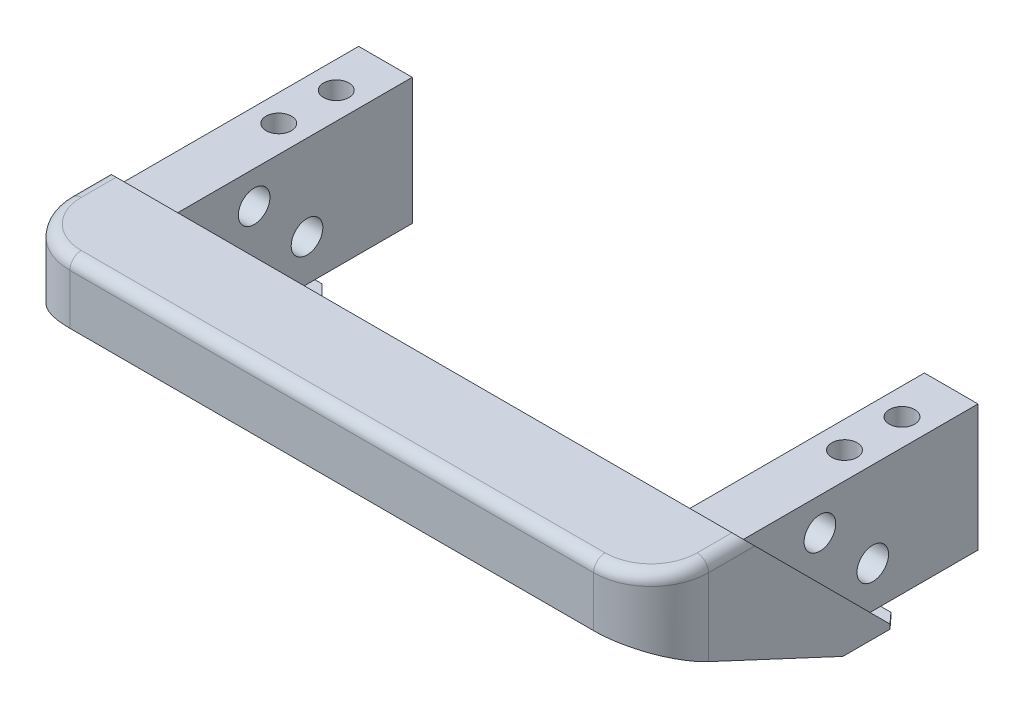
SolidWorks part; units mm, degrees
ref_plane "Front Plane" through (0, 0, 0) normal (0, 0, 1) x (1, 0, 0)
ref_plane "Top Plane" through (0, 0, 0) normal (0, 1, 0) x (1, 0, 0)
ref_plane "Right Plane" through (0, 0, 0) normal (1, 0, 0) x (0, 0, -1)
sketch "Sketch1" plane through (0, 0, 0) normal (1, 0, 0) x (0, 0, -1)
  line L0 (0, 0) -> (0, 50.8)
  line L5 (0, 50.8) -> (50.8, 0)
  line L6 (50.8, 0) -> (0, 0)
  dimension "D1" = 45
  dimension "D2" = 50.8
extrude "Boss-Extrude1" add sketch "Sketch1" along normal blind 222.25
sketch "Sketch3" plane through (0, 0, 0) normal (0, 0, 1) x (1, 0, 0)
  line L0 (196.85, 50.8) -> (196.85, 0) construction
  line L1 (218.875, 47.425) -> (200.225, 47.425)
  line L2 (218.875, 47.425) -> (218.875, 3.375)
  line L3 (218.875, 3.375) -> (200.225, 3.375)
  line L4 (200.225, 47.425) -> (200.225, 3.375)
  line L5 (222.25, 50.8) -> (222.25, 0) construction
  line L6 (222.25, 50.8) -> (0, 50.8) construction
  line L7 (222.25, 0) -> (0, 0) construction
  dimension "D1" = 3.375
  dimension "D2" = 3.375
  dimension "D3" = 3.375
  dimension "D4" = 18.65
  dimension "D5" = 25.4
extrude "Boss-Extrude3" add sketch "Sketch3" against normal blind 85 contours L1 L4 L3 L2 region at (209.55, 25.4, 0)
sketch "Sketch15" plane through (0, 47.425, 0) normal (0, 1, 0) x (1, 0, 0)
  circle A0 centre (209.55, 67.8714) radius 4.4196
  circle A1 centre (209.55, 47.8714) radius 4.4196
  dimension "D1" = 8.8392
  dimension "D2" = 8.8392
extrude "Cut-Extrude6" cut sketch "Sketch15" against normal blind 15
sketch "Sketch16" plane through (200.225, 0, 0) normal (-1, 0, 0) x (0, 0, 1)
  circle A0 centre (-29.9942, 36.0705) radius 5.5
  circle A1 centre (-48.379, 17.6857) radius 5.5
  dimension "D1" = 11
  dimension "D2" = 11
extrude "Cut-Extrude7" cut sketch "Sketch16" against normal through all
ref_plane "Plane1" through (111.125, 0, 0) normal (-1, 0, 0) x (0, 0, 1)
mirror "Mirror1" about plane through (111.125, 0, 0) normal (-1, 0, 0) of "Cut-Extrude7", "Boss-Extrude3", "Cut-Extrude6"
sketch "Sketch4" plane through (222.25, 0, 0) normal (1, 0, 0) x (0, 0, -1)
  line L0 (-5, 50.8) -> (-26.1464, 36.606)
  line L3 (0, 0) -> (0, 50.8)
  line L4 (0, 50.8) -> (-5, 50.8)
  line L5 (0, 0) -> (-5, 0)
  line L6 (-15, 0) -> (-5, 0)
  line L7 (-5, 50.8) -> (-5, 0) construction
  arc A0 (-15, 0) -> (-26.1464, 36.606) centre (-15, 20) cw
  dimension "D2" = 20
  dimension "D1" = 10
  dimension "D3" = 5
extrude "Boss-Extrude4" [suppressed] add sketch "Sketch4" against normal up to surface (222.25 mm away) up to face at (0, 16.9333, -16.9333)
sketch "Sketch7" plane through (222.25, 0, 0) normal (1, 0, 0) x (0, 0, -1)
  line L0 (0, 50.8) -> (-32.1286, 50.8)
  line L2 (-32.1286, 29.3441) -> (30.8, 0)
  line L3 (0, 0) -> (50.8, 0) construction
  line L4 (30.8, 0) -> (50.8, 0)
  line L5 (50.8, 0) -> (0, 50.8)
  line L8 (-32.1286, 50.8) -> (-32.1286, 29.3441)
  point P1 (-32.1286, 29.3234)
  dimension "D1" = 20
  dimension "D2" = 20
  dimension "D3" = 32.1286
extrude "Boss-Extrude5" add sketch "Sketch7" against normal up to surface (222.25 mm away) up to face at (0, 16.9333, -16.9333)
sketch "Sketch8" plane through (222.25, 0, 0) normal (1, 0, 0) x (0, 0, -1)
  line L0 (-32.1286, 29.3441) -> (30.8, 0) construction
  line L1 (0, 14.3623) -> (30.8, 0)
  line L2 (0, 14.3623) -> (0, 0)
  line L3 (0, 0) -> (30.8, 0)
extrude "Cut-Extrude3" cut sketch "Sketch8" against normal up to surface (222.25 mm away) up to face at (0, 24.2177, 2.2429)
sketch "Sketch9" plane through (222.25, 0, 0) normal (1, 0, 0) x (0, 0, -1)
  line L0 (50.8, 0) -> (73.6991, 0) construction
  line L1 (50.8, 0) -> (51, -0.2)
  line L2 (30.8, 0) -> (34.6333, -1.7875)
  line L3 (-32.1286, 29.3441) -> (30.8, 0) construction
  line L4 (50.8, 0) -> (0, 50.8) construction
  line L5 (51, -0.2) -> (54.7, -0.2)
  line L6 (54.7, -0.2) -> (54.7, -1.7875)
  line L7 (54.7, -1.7875) -> (34.6333, -1.7875)
  line L8 (30.8, 0) -> (50.8, 0) construction
  line L9 (30.8, 0) -> (50.8, 0)
  line M9 (30.8, 0) -> (50.8, 0)
  dimension "D1" = 0.2
  dimension "D2" = 1.5875
  dimension "D3" = 3.9
extrude "Boss-Extrude6" add sketch "Sketch9" against normal up to surface (222.25 mm away) contours L7 L6 L5 L1 L2 M9 region at (222.25, -0.8829, -43.5006) up to face at (0, 26.1888, -3.4685)
sketch "Sketch10" plane through (0, -1.7875, 0) normal (0, -1, 0) x (1, 0, 0)
  line L0 (218.8722, -54.7) -> (222.25, -51)
  line L1 (0, -54.7) -> (222.25, -54.7) construction
  line L2 (222.25, -54.7) -> (222.25, -34.6333) construction
  line L3 (222.25, -54.7) -> (218.8722, -54.7)
  line L4 (222.25, -54.7) -> (222.25, -51)
  line L6 (111.125, -54.7) -> (197.8722, -54.7)
  line L7 (111.125, -54.7) -> (111.125, -51)
  line L8 (111.125, -51) -> (197.8722, -51)
  line L9 (197.8722, -54.7) -> (197.8722, -51)
  line L10 (0, -9.2034) -> (222.25, -9.2034) construction
  line L11 (0, 32.1286) -> (0, -34.6333) construction
  line L12 (222.25, 32.1286) -> (222.25, -34.6333) construction
  line L13 (111.125, -9.2034) -> (111.125, -68.2914) construction
  line L14 (0, -51) -> (222.25, -51) construction
  dimension "D1" = 3.3778
  dimension "D2" = 3.7
  dimension "D3" = 21
extrude "Cut-Extrude4" cut sketch "Sketch10" against normal up to next
mirror "Mirror2" about plane through (111.125, 0, 0) normal (-1, 0, 0) of "Cut-Extrude4"
chamfer "Chamfer1" distance 3.5 angle 45 2 edges at (24.3778, -0.9938, -54.7) (197.8722, -0.9938, -54.7)
sketch "Sketch11" plane through (0, -1.7875, 0) normal (0, -1, 0) x (1, 0, 0)
  line L0 (111.125, -51) -> (111.125, -11.1659) construction
  line L1 (197.8722, -51) -> (24.3778, -51) construction
  line L2 (0, -34.6333) -> (222.25, -34.6333) construction
  line L3 (66.125, -51) -> (156.125, -51)
  line L4 (66.125, -51) -> (66.125, -34.6333)
  line L5 (66.125, -34.6333) -> (156.125, -34.6333)
  line L6 (156.125, -51) -> (156.125, -34.6333)
  dimension "D1" = 90
extrude "Cut-Extrude5" cut sketch "Sketch11" against normal up to next
fillet "Fillet1" radius 4 1 edges at (111.125, -1.7875, -34.6333) tangent propagation no
fillet "Fillet2" radius 20 2 edges at (0, 40.0721, 32.1286) (222.25, 40.0721, 32.1286)
fillet "Fillet3" radius 4 5 edges at (0, 50.8, 6.0643) (5.8579, 50.8, 26.2708) (222.25, 50.8, 6.0643) (216.3921, 50.8, 26.2708) (111.125, 50.8, 32.1286)
equation "\"Length\"= 222.25"
equation "\"Height\"= 50.8"
equation "\"D2@Sketch1\"=\"Height\""
equation "\"D1@Boss-Extrude1\"=\"Length\""
equation "\"Slot\"= 3.175 + 0.2"
equation "\"D1@Sketch3\"=\"Slot\""
equation "\"D2@Sketch3\"=\"Slot\""
equation "\"D3@Sketch3\"=\"Slot\""
equation "\"Inside_Slot\"= 25.4 - ( 2 * 3.175 ) - ( 2 * 0.2 )"
equation "\"D4@Sketch3\"=\"Inside_Slot\""
